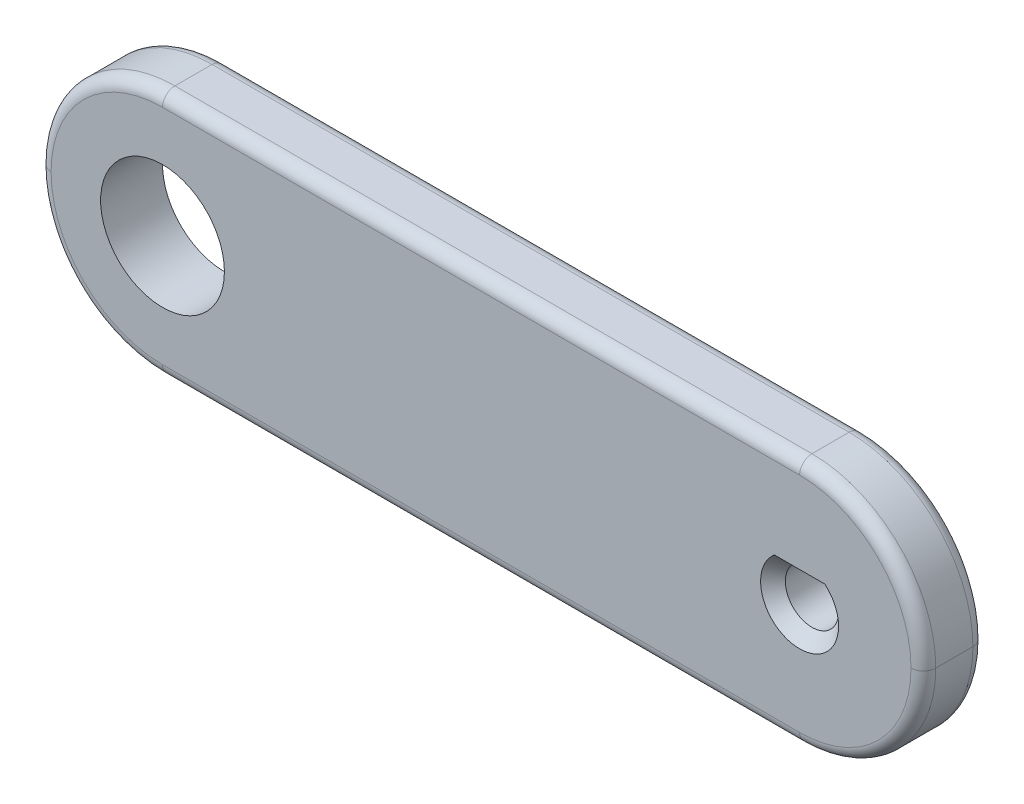
SolidWorks part; units mm, degrees
ref_plane "Alzado" through (0, 0, 0) normal (0, 0, 1) x (1, 0, 0)
ref_plane "Planta" through (0, 0, 0) normal (0, 1, 0) x (1, 0, 0)
ref_plane "Vista lateral" through (0, 0, 0) normal (1, 0, 0) x (0, 0, -1)
sketch "Croquis1" plane through (0, 0, 0) normal (0, 0, 1) x (1, 0, 0)
  line L1 (0, 0) -> (-71.46, 0)
  line L2 (0, 0) -> (0, 20)
  line L3 (0, 20) -> (-71.46, 20)
  line L4 (-71.46, 0) -> (-71.46, 20)
  circle A0 centre (-61.46, 10) radius 5
  circle A1 centre (-10, 10) radius 5
  point P10 (0, 10)
  dimension "D2" = 10
  dimension "D3" = 10
  dimension "D1" = 10
  dimension "D4" = 20
  dimension "D5" = 51.46
  dimension "D6" = 10
extrude "Saliente-Extruir1" add sketch "Croquis1" along normal blind 5
fillet "Redondeo2" radius 10 4 edges at (-71.46, 0, 2.5) (-71.46, 20, 2.5) (0, 0, 2.5) (0, 20, 2.5)
fillet "Redondeo3" radius 1 12 edges at (-2.9289, 17.0711, 0) (-2.9289, 2.9289, 0) (-35.73, 0, 0) (-68.5311, 2.9289, 0) (-68.5311, 17.0711, 0) (-2.9289, 17.0711, 5) (-2.9289, 2.9289, 5) (-35.73, 0, 5) (-68.5311, 2.9289, 5) (-68.5311, 17.0711, 5) (-35.73, 20, 0) (-35.73, 20, 5)
sketch "Croquis2" plane through (0, 0, 5) normal (0, 0, 1) x (1, 0, 0)
  line L0 (-11.6317, 11.4) -> (-8.3683, 11.4)
  circle A0 centre (-10, 10) radius 5
  arc A1 (-11.6317, 11.4) -> (-8.3683, 11.4) centre (-10, 10) ccw
  dimension "D1" = 4.3
  dimension "D2" = 1.4
extrude "Saliente-Extruir2" add sketch "Croquis2" against normal up to surface (5 mm away) up to face at (-35.73, 10, 0)
chamfer "Chaflán1" distance 1 angle 45 2 edges at (-10, 7.85, 5) (-10, 11.4, 5)
